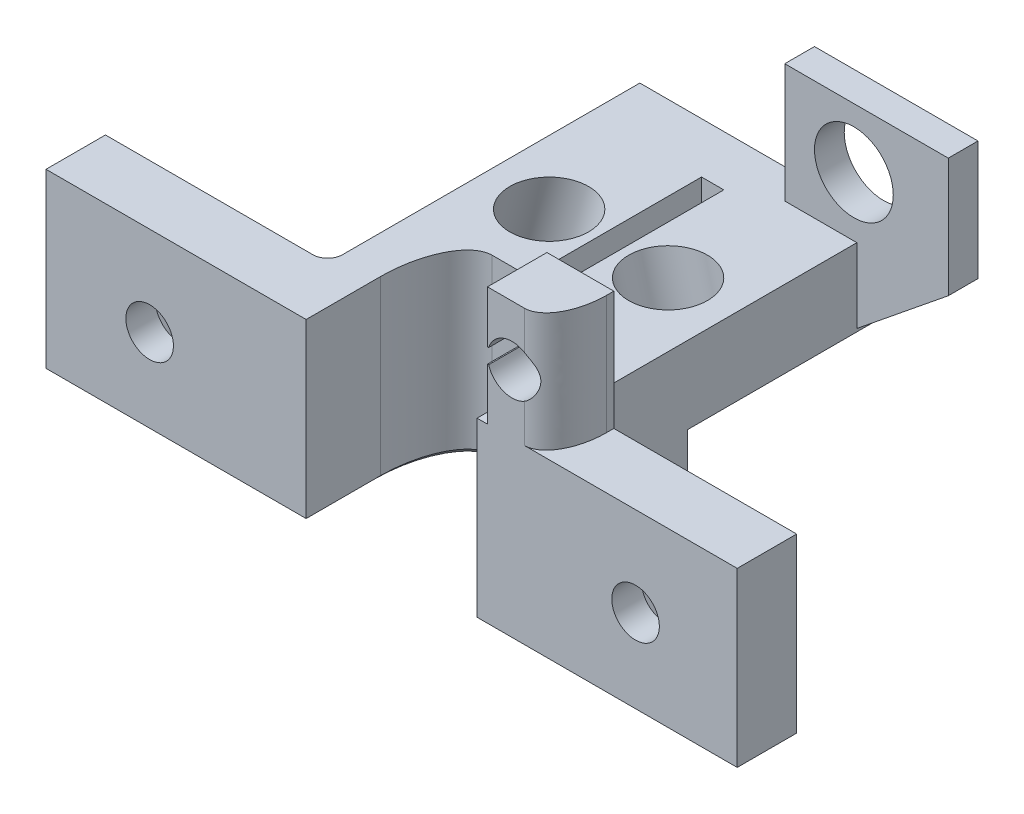
SolidWorks part; units mm, degrees
ref_plane "Front Plane" through (0, 0, 0) normal (0, 0, 1) x (1, 0, 0)
ref_plane "Top Plane" through (0, 0, 0) normal (0, 1, 0) x (1, 0, 0)
ref_plane "Right Plane" through (0, 0, 0) normal (1, 0, 0) x (0, 0, -1)
sketch "Sketch1" plane through (0, 0, 0) normal (0, 1, 0) x (1, 0, 0)
  line L0 (-3.25, -5) -> (-23.25, -5)
  line L1 (-3.25, -5) -> (3.25, -5) construction
  line L2 (-3.25, -5) -> (-3.25, 5) construction
  line L3 (-3.25, 5) -> (3.25, 5)
  line L4 (3.25, -5) -> (3.25, 5) construction
  line L5 (-3.25, -5) -> (3.25, 5) construction
  line L6 (-3.25, 5) -> (3.25, -5) construction
  line L7 (-23.25, -5) -> (-23.25, -1)
  line L8 (-23.25, -1) -> (-9.3, -1)
  line L9 (3.25, -5) -> (23.25, -5)
  line L10 (23.25, -5) -> (23.25, -3)
  line L12 (-8.3, 0) -> (-8.3, 6.6)
  line L13 (-8.3, 6.6) -> (8.3, 6.6)
  line L14 (8.3, 0) -> (8.3, 6.6)
  line L15 (-5.7498, 0) -> (-5.7498, -5)
  line L16 (5.7487, 0) -> (5.7487, -5)
  line L17 (23.25, -3) -> (23.25, -1)
  line L18 (23.25, -1) -> (9.3, -1)
  arc A0 (-9.3, -1) -> (-8.3, 0) centre (-9.3, 0) ccw
  arc A1 (9.3, -1) -> (8.3, 0) centre (9.3, 0) cw
  ellipse E0 centre (-3.25, 0) end of major axis (-3.25, 5) minor radius 2.4998 (-3.25, 5) -> (-3.25, -5) ccw
  ellipse E1 centre (3.25, 0) end of major axis (3.25, 5) minor radius 2.4987 (3.25, -5) -> (3.25, 5) ccw
  point P0 (0, 0)
  dimension "D6" = 1
  dimension "D7" = 4
  dimension "D12" = 1
  dimension "D1" = 6.5
  dimension "D2" = 10
  dimension "D3" = 20
  dimension "D4" = 4
  dimension "D5" = 20
  dimension "D8" = 16.6
  dimension "D9" = 1.6
  dimension "D10" = 5.05
  dimension "D11" = 5.05
extrude "Boss-Extrude1" add sketch "Sketch1" along normal blind 12
sketch "Sketch2" plane through (0, 0, 1) normal (0, 0, -1) x (-1, 0, 0)
  line L0 (-23.3943, 12) -> (-9.4265, 0) construction
  line L1 (-23.25, 0) -> (-9.2822, 12) construction
  line L2 (23.25, 12) -> (9.3079, 0) construction
  line L3 (23.25, 0) -> (9.3, 0) construction
  line L4 (23.25, 0) -> (9.2822, 12) construction
  line L5 (-16.4104, 6) -> (-16.4104, -2.9743) construction
  line L6 (-16.4104, -0.7517) -> (-16.4104, 3) construction
  line L10 (16.2789, 6) -> (16.2789, -2.9743) construction
  line L11 (20.1472, 6) -> (18.2131, 9.35)
  line L12 (-12.5422, 6) -> (-14.4763, 9.35)
  line L13 (-14.4763, 9.35) -> (-18.3445, 9.35)
  line L14 (-18.3445, 9.35) -> (-20.2787, 6)
  line L15 (-20.2787, 6) -> (-18.3445, 2.65)
  line L16 (18.2131, 9.35) -> (14.3448, 9.35)
  line L17 (14.3448, 9.35) -> (12.4107, 6)
  line L18 (-18.3445, 2.65) -> (-14.4763, 2.65)
  line L19 (-14.4763, 2.65) -> (-12.5422, 6)
  line L20 (12.4107, 6) -> (14.3448, 2.65)
  line L21 (14.3448, 2.65) -> (18.2131, 2.65)
  line L22 (18.2131, 2.65) -> (20.1472, 6)
  circle A0 centre (-16.4104, 6) radius 3.35 construction
  circle A1 centre (16.2789, 6) radius 3.35 construction
  point P32 (11.4039, 0.6926)
  dimension "D1" = 6.7
  dimension "D2" = 6.7
extrude "Cut-Extrude1" cut sketch "Sketch2" against normal blind 2
sketch "Sketch3" plane through (0, 12, 0) normal (0, 1, 0) x (1, 0, 0)
  line L0 (-3.25, 5) -> (-3.25, 12.9854) construction
  line L1 (3.25, 5) -> (3.25, 12.9854) construction
  line L2 (-8.3, 6.6) -> (8.3, 6.6)
  line L3 (-8.1382, 9.4853) -> (3.25, 9.4853) construction
  line L4 (-10.9928, 20.2416) -> (10.7178, 20.2416) construction
  line L5 (-8.3, 6.6) -> (-8.3, 20)
  line L6 (-8.3, 20) -> (8.3, 20)
  line L7 (8.3, 20) -> (8.3, 6.6)
  line L8 (-5.7498, -5) -> (-23.25, -5) construction
  circle A1 centre (3.25, 9.4853) radius 2.5 construction
  circle A3 centre (0, 0) radius 13.8 construction
  circle A4 centre (-3.25, 9.4853) radius 2.85 construction
  circle A5 centre (3.25, 9.4853) radius 2.85 construction
  circle A7 centre (0, 0) radius 13 construction
  dimension "D1" = 20.2416
  dimension "D2" = 25
  dimension "D3" = 27.6
  dimension "D4" = 5.7
  dimension "D5" = 5.7
  dimension "D9" = 26
extrude "Boss-Extrude2" add sketch "Sketch3" against normal blind 5.2
sketch "Sketch4" [suppressed] plane through (0, 6.8, 0) normal (0, -1, 0) x (1, 0, 0)
  line L0 (-8.3, -6.6) -> (8.3, -6.6)
  line L1 (8.3, -6.6) -> (8.3, -11.9594)
  line L2 (-8.3, -6.6) -> (-8.3, -9.2406)
  ellipse E1 centre (0, -10.6) end of major axis (8.3, -12.6) minor radius 3.3362 (-8.3, -9.2406) -> (8.3, -11.9594) ccw
extrude "Boss-Extrude3" [suppressed] add sketch "Sketch4" along normal blind 5
chamfer "Chamfer1" [suppressed] distance 0.5 angle 45
sketch "Sketch5" plane through (0, 0, 1) normal (0, 0, -1) x (-1, 0, 0)
  line L0 (12.4107, 6) -> (20.1472, 6) construction
  line L1 (20.1472, 6) -> (18.2131, 9.35) construction
  line L2 (20.1472, 6) -> (18.2131, 9.35) construction
  line L3 (16.2789, 9.35) -> (16.2789, 2.65) construction
  line L4 (18.2131, 9.35) -> (14.3448, 9.35) construction
  line L5 (14.3448, 2.65) -> (18.2131, 2.65) construction
  line L6 (-16.4104, 9.35) -> (-16.4104, 2.65) construction
  line L7 (-14.4763, 9.35) -> (-18.3445, 9.35) construction
  line L8 (-18.3445, 2.65) -> (-14.4763, 2.65) construction
  line L9 (-20.2787, 6) -> (-12.5422, 6) construction
  circle A0 centre (-16.4104, 6) radius 1.6
  circle A1 centre (16.2789, 6) radius 1.6
  dimension "D1" = 3.2
  dimension "D2" = 3.2
extrude "Cut-Extrude2" cut sketch "Sketch5" against normal blind 5
sketch "Sketch6" plane through (0, 12, 0) normal (0, 1, 0) x (1, 0, 0)
  line L0 (5.7487, -5) -> (23.25, -5) construction
  line L1 (6.4487, -5) -> (10.9487, -5)
  line L2 (6.4487, -5) -> (6.4487, -1)
  line L3 (6.4487, -1) -> (10.9487, -1)
  line L4 (10.9487, -5) -> (10.9487, -1)
  line L6 (5.7487, 0) -> (5.7487, -5) construction
  dimension "D1" = 4
  dimension "D2" = 0.7
  dimension "D3" = 4.5
extrude "Boss-Extrude4" add sketch "Sketch6" along normal blind 8
sketch "Sketch7" plane through (0, 0, 1) normal (0, 0, -1) x (-1, 0, 0)
  line L1 (-6.4487, 12) -> (-6.4487, 20) construction
  line L2 (-6.4487, 16) -> (-15.0595, 16) construction
  line L4 (-5.584, 16.5) -> (-7.9994, 16.5)
  line L5 (-5.584, 16.5) -> (-5.584, 15.5)
  line L6 (-5.584, 15.5) -> (-7.9994, 15.5)
  line L7 (-7.9994, 16.5) -> (-7.9994, 15.5)
  line L8 (-5.584, 16.5) -> (-7.9994, 15.5) construction
  line L9 (-5.584, 15.5) -> (-7.9994, 16.5) construction
  circle A0 centre (-8.0987, 16) radius 1.65
  point P6 (-6.7917, 16)
  line M11 (-6.4487, 12) -> (-6.4487, 20)
  dimension "D1" = 3.3
  dimension "D2" = 1
extrude "Cut-Extrude4" cut sketch "Sketch7" against normal blind 7 contours L4 A0 L6 L7 | A0 L4 L7 L6 | A0 L6 M11 | A0 L4 M11
sketch "Sketch8" plane through (0, 12, 0) normal (0, 1, 0) x (1, 0, 0)
  line L0 (8.3, 12.6) -> (-8.3, 12.6) construction
  line L1 (0, 12.6) -> (0, 3.5286) construction
  line L2 (-9.6265, 9.6) -> (9.6265, 9.6) construction
  line L4 (-3.25, 5) -> (3.25, 5) construction
  circle A0 centre (-4, 9.6) radius 2.65
  point P10 (0, 9.6)
  dimension "D2" = 5.3
  dimension "D3" = 7.6
  dimension "D1" = 3
  dimension "D4" = 4
sketch3d "3DSketch1"
  line L0 (0, 24, -5) -> (8.119, -6.3005, -5) construction
  line L1 (-3.25, 12, -5) -> (3.25, 12, -5) construction
  line L2 (3.25, 12, -5) -> (-3.25, 12, -5) construction
  line L3 (0, 12, -5) -> (0, -3.1746, -5) construction
  line L4 (0, 12, -5) -> (0, 24, -5) construction
  line L5 (0, 24, -5) -> (-8.2564, -6.8133, -5) construction
  point P7 (0, 12, -5)
  dimension "D1" = 12
  dimension "D2" = 15
  dimension "D3" = 15
extrude "Cut-Extrude5" cut sketch "Sketch8" along direction (-0.2588, -0.9659, 0) on the side against the normal blind 7
ref_plane "Plane1" through (8.119, -6.3005, -5) normal (0.2588, -0.9659, 0) x (-0.9659, -0.2588, 0)
sketch "Sketch10" plane through (0, 12, 0) normal (0, 1, 0) x (1, 0, 0)
  line L0 (-8.3, 12.6) -> (8.3, 12.6) construction
  line L1 (0, 12.6) -> (0, 2.6194) construction
  line L2 (-11.9688, 9.6) -> (11.9688, 9.6) construction
  line L3 (0, 5) -> (8.119, 5) construction
  circle A0 centre (4, 9.6) radius 2.65
  point P10 (0, 9.6)
  dimension "D3" = 5.3
  dimension "D1" = 3
  dimension "D2" = 4
  dimension "D4" = 7.6
extrude "Cut-Extrude6" cut sketch "Sketch10" along direction (0.2588, -0.9659, 0) on the side against the normal blind 7
chamfer "Chamfer2" distance 2 angle 45 2 edges at (7.8743, 12, 1) (8.5929, 12, 0.7071)
chamfer "Chamfer3" [suppressed] distance 1 angle 45
sketch "Sketch12" plane through (0, 12, 0) normal (0, 1, 0) x (1, 0, 0)
  line L0 (5.7487, 0) -> (5.7487, 22.8142) construction
  line L1 (6.4487, 1) -> (6.4487, 22.8142) construction
  line L2 (10.9487, -5) -> (23.25, -5) construction
  line L3 (6.4487, 20) -> (14.4487, 20)
  line L4 (6.4487, 20) -> (6.4487, 18)
  line L5 (6.4487, 18) -> (14.4487, 18)
  line L6 (14.4487, 20) -> (14.4487, 18)
  line L8 (6.4487, 20) -> (3.4487, 20)
  line L9 (6.4487, 20) -> (6.4487, 18)
  line L10 (6.4487, 18) -> (3.4487, 18)
  line L11 (3.4487, 20) -> (3.4487, 18)
  line M8 (8.3, 1) -> (8.3, 20)
  dimension "D1" = 8
  dimension "D2" = 2
  dimension "D3" = 23
  dimension "D4" = 3
extrude "Boss-Extrude5" add sketch "Sketch12" along normal blind 8 contours L8 L11 L10 L4 | L6 L3 L5 M8 | L4 L5 L3 M8
sketch "Sketch13" plane through (0, 0, -20) normal (0, 0, -1) x (-1, 0, 0)
  line L0 (-6.4487, 20) -> (-6.4487, 12) construction
  line L1 (8.3, 12) -> (-3.4487, 12) construction
  line L3 (-6.4487, 16) -> (-16.867, 16) construction
  circle A0 centre (-8.0987, 16) radius 1.65 construction
  circle A1 centre (-8.0987, 16) radius 2.65
  dimension "D1" = 3.3
  dimension "D2" = 5.3
  dimension "D3" = 1.8513
extrude "Cut-Extrude7" cut sketch "Sketch13" against normal blind 3
chamfer "Chamfer4" distance 5 angle 51 1 edges at (8.3, 12, -19)
sketch "Sketch16" plane through (0, 6.8, 0) normal (0, -1, 0) x (1, 0, 0)
  line L0 (-8.3, -6.6) -> (8.3, -6.6) construction
  line L1 (0, -6.6) -> (0, -20) construction
  line L2 (-8.3, -20) -> (8.3, -20) construction
  line L4 (-0.75, -16.6) -> (0.75, -16.6)
  line L5 (-0.75, -16.6) -> (-0.75, -6.6)
  line L6 (-0.75, -6.6) -> (0.75, -6.6)
  line L7 (0.75, -16.6) -> (0.75, -6.6)
  line L8 (-0.75, -16.6) -> (0.75, -6.6) construction
  line L9 (-0.75, -6.6) -> (0.75, -16.6) construction
  point P8 (0, -11.6)
  dimension "D1" = 1.5
  dimension "D2" = 10
extrude "Cut-Extrude8" cut sketch "Sketch16" against normal blind 11
chamfer "Chamfer5" distance 0.4 angle 45 16 edges at (5.7487, 0, 2.5) (14.4993, 0, 5) (23.25, 0, 3) (16.275, 0, 1) (8.5929, 0, 0.7071) (8.3, 0, -3.3) (0, 0, -6.6) (-8.3, 0, -3.3) (-8.5929, 0, 0.7071) (-16.275, 0, 1) (-23.25, 0, 3) (-14.4999, 0, 5) (-5.7498, 0, 2.5) (-5.0176, 0, -3.5355) (0, 0, -5) (5.0168, 0, -3.5355)
sketch "Sketch18" plane through (0, 12, 0) normal (0, 1, 0) x (1, 0, 0)
  circle A0 centre (0, 0) radius 11.76 construction
  dimension "D1" = 23.52
fillet "Fillet1" radius 2 1 edges at (10.9487, 16, 5)
